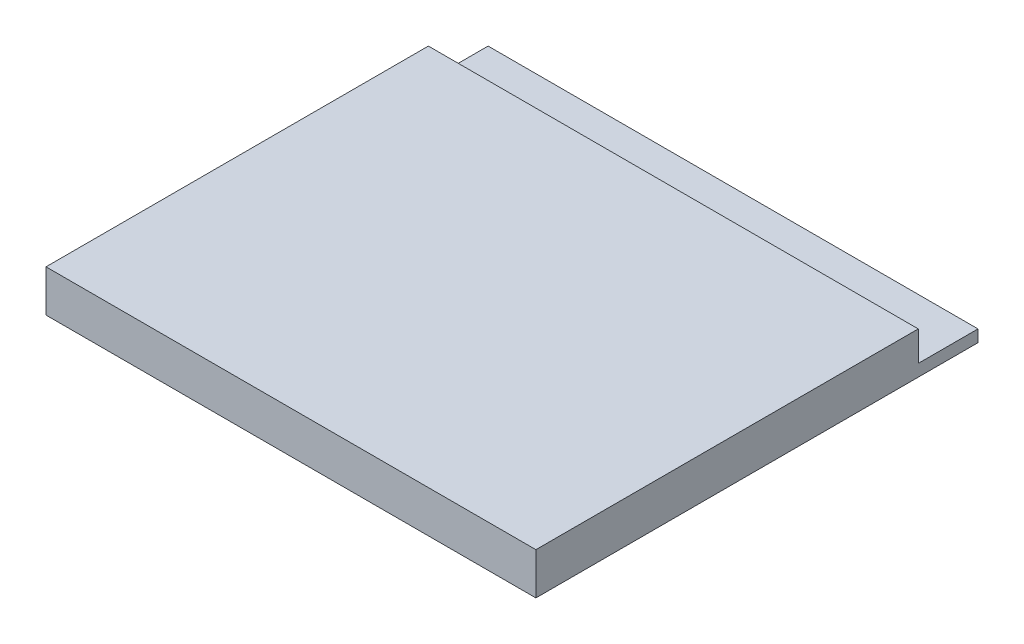
SolidWorks part; units mm, degrees
ref_plane "Alzado" through (0, 0, 0) normal (0, 0, 1) x (1, 0, 0)
ref_plane "Planta" through (0, 0, 0) normal (0, 1, 0) x (1, 0, 0)
ref_plane "Vista lateral" through (0, 0, 0) normal (1, 0, 0) x (0, 0, -1)
sketch "Croquis1" plane through (0, 0, 0) normal (0, 1, 0) x (1, 0, 0)
  line L0 (0, 32) -> (41, 32)
  line L1 (0, 37) -> (41, 37)
  line L2 (0, 37) -> (0, 0)
  line L3 (0, 0) -> (41, 0)
  line L4 (41, 37) -> (41, 0)
  dimension "D1" = 41
  dimension "D2" = 37
  dimension "D3" = 32
extrude "Saliente-Extruir2" add sketch "Croquis1" along normal blind 3.5 contours L4 L0 L2 L3 region at (20.5, 0, -16)
extrude "Saliente-Extruir3" add sketch "Croquis1<4>" along normal blind 1 contours L4 L1 L2 L0 region at (20.5, 0, -34.5)
sketch "Croquis1<4>" plane through (0, 0, 0) normal (0, 1, 0) x (1, 0, 0) same geometry as "Croquis1"
